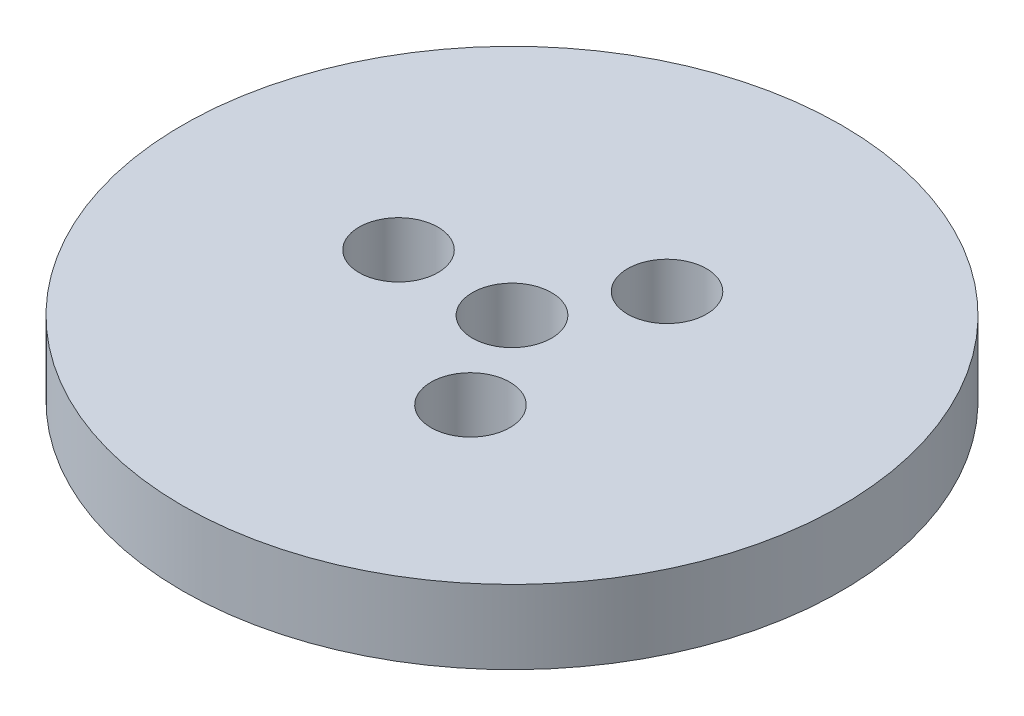
SolidWorks part; units mm, degrees
ref_plane "Front Plane" through (0, 0, 0) normal (0, 0, 1) x (1, 0, 0)
ref_plane "Top Plane" through (0, 0, 0) normal (0, 1, 0) x (1, 0, 0)
ref_plane "Right Plane" through (0, 0, 0) normal (1, 0, 0) x (0, 0, -1)
sketch "Sketch1" plane through (0, 0, 0) normal (0, 1, 0) x (1, 0, 0)
  circle A0 centre (0, 0) radius 62.5
  dimension "FLANGE_OD" = 125
extrude "Boss-Extrude1" add sketch "Sketch1" along normal blind 14
sketch "Sketch2" plane through (0, 0, 0) normal (0, 1, 0) x (1, 0, 0)
  circle A0 centre (0, 0) radius 7.5
  dimension "BORE_D" = 15
extrude "Cut-Extrude1" cut sketch "Sketch2" along normal through all
sketch "Sketch3" plane through (0, 14, 0) normal (0, 1, 0) x (1, 0, 0)
  circle A0 centre (0, 0) radius 21.5244 construction
  circle A1 centre (-21.5244, 0) radius 7.4831
  dimension "BOLT_D" = 14.9663
  dimension "BOLT_PCD" = 43.0488
extrude "Cut-Extrude2" cut sketch "Sketch3" against normal blind 13.0004
pattern_circular "CirPattern1" count 3 over 360 about axis through (0, 0, 0) along (0, 1, 0) of "Cut-Extrude2"
